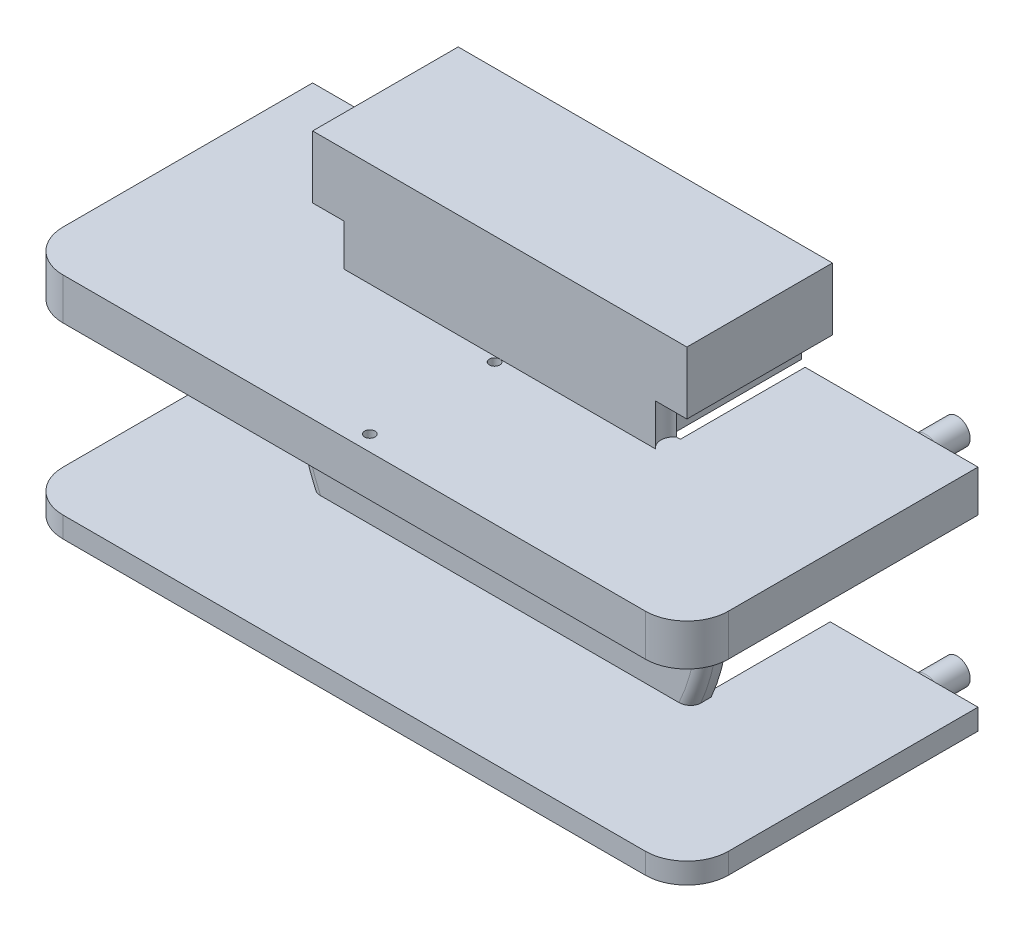
SolidWorks part; units mm, degrees
material "UNOBTANIUM"
ref_plane "Top Plane" through (0, 0, 0) normal (0, 0, 1) x (1, 0, 0)
ref_plane "Right Plane" through (0, 0, 0) normal (0, 1, 0) x (1, 0, 0)
ref_plane "Front Plane" through (0, 0, 0) normal (1, 0, 0) x (0, 0, -1)
ref_axis "x-axis" through (-17.6, 0, 0) along (1, 0, 0)
ref_axis "y-axis" through (0, -9.7375, 0) along (0, 1, 0)
ref_axis "z-axis" through (0, 0, 8.775) along (0, 0, -1)
sketch "Sketch1" plane through (0, 0, 0) normal (0, 0, 1) x (1, 0, 0)
  line L0 (-11, 6) -> (-11, 11)
  line L1 (-11, -6) -> (11, -6)
  line L2 (-11, -6) -> (-11, 6)
  line L3 (-11, 6) -> (11, 6) construction
  line L4 (11, -6) -> (11, 6)
  line L5 (-11, -6) -> (11, 6) construction
  line L6 (-11, 6) -> (11, -6) construction
  line L7 (-11, 11) -> (11, 11)
  line L8 (11, 11) -> (11, 6)
  circle A0 centre (0, 0) radius 9.25 construction
  point P0 (0, 0)
  dimension "D1" = 18.5
  dimension "D2" = 22
  dimension "D3" = 12
  dimension "D4" = 5
extrude "Boss-Extrude1" add sketch "Sketch1" along normal blind 1
sketch "Sketch2" plane through (0, 0, 0) normal (0, 0, -1) x (-1, 0, 0)
  circle A0 centre (0, 0) radius 1.51
  dimension "D1" = 3.02
extrude "Boss-Extrude2" add sketch "Sketch2" along normal blind 5.5
sketch "Sketch3" plane through (0, 0, 0) normal (0, 0, -1) x (-1, 0, 0)
  line L0 (11, -6) -> (-11, 6) construction
  circle A0 centre (0, 0) radius 3.5
  dimension "D1" = 7
extrude "Boss-Extrude3" add sketch "Sketch3" along normal blind 1
sketch "Sketch4" plane through (0, 0, 0) normal (0, 0, -1) x (-1, 0, 0)
  line L0 (11, -6) -> (-11, -6) construction
  line L1 (11, 11) -> (9, 11)
  line L2 (11, 11) -> (11, -6)
  line L3 (11, -6) -> (9, -6)
  line L4 (9, 11) -> (9, -6)
  line L5 (0, -6) -> (0, 11) construction
  line L7 (-9, 11) -> (-9, -6)
  line L8 (-11, -6) -> (-9, -6)
  line L9 (-11, 11) -> (-11, -6)
  line L10 (-11, 11) -> (-9, 11)
  line L11 (11, 11) -> (-11, 11) construction
  dimension "D1" = 2
extrude "Boss-Extrude4" add sketch "Sketch4" along normal blind 6
sketch "Sketch5" plane through (0, 0, 0) normal (0, 0, -1) x (-1, 0, 0)
  line L0 (-9, -6) -> (-9, 11) construction
  line L1 (9, 11) -> (-9, 11)
  line L2 (9, 11) -> (9, 9)
  line L3 (9, 9) -> (-9, 9)
  line L4 (-9, 11) -> (-9, 9)
  dimension "D1" = 2
extrude "Boss-Extrude5" add sketch "Sketch5" along normal up to surface (6 mm away) up to face at (-10, 2.5, -6)
sketch "Sketch6" plane through (11, 0, 0) normal (1, 0, 0) x (0, 0, -1)
  line L0 (-1, -6) -> (-1, 11) construction
  line L1 (6, -6) -> (-1, -6)
  line L2 (6, -6) -> (6, -4)
  line L3 (6, -4) -> (-1, -4)
  line L4 (-1, -6) -> (-1, -4)
  line L6 (6, 11) -> (6, -6) construction
  line L7 (-1, 6) -> (6, 6)
  line L8 (-1, 6) -> (-1, 4)
  line L9 (-1, 4) -> (6, 4)
  line L10 (6, 6) -> (6, 4)
  line L11 (2.5, 4) -> (2.5, -4) construction
  line L12 (0, 0) -> (2.5, 0) construction
  line L13 (0, -6) -> (0, 6) construction
  point P21 (2.5, 0)
  dimension "D1" = 2
extrude "Boss-Extrude6" add sketch "Sketch6" along normal blind 5
mirror "Mirror1" about plane through (0, 0, 0) normal (1, 0, 0) of "Boss-Extrude6"
sketch "Sketch7" plane through (0, 0, -6) normal (0, 0, -1) x (-1, 0, 0)
  line L0 (-9, -6) -> (-9, 9) construction
  line L1 (-9, 0) -> (-9, 9)
  line L2 (-9, 9) -> (0, 9)
  line L3 (-9, 0) -> (-9, -6)
  line L4 (-9, -6) -> (-6.7082, -6)
  line L5 (11, -6) -> (-11, -6) construction
  arc A0 (0, 9) -> (-6.7082, -6) centre (0, 0) ccw
  line M18 (-9, -6) -> (-9, 9)
  line M19 (-9, 9) -> (9, 9)
extrude "Boss-Extrude7" add sketch "Sketch7" against normal up to surface (6 mm away) contours A0 L4 M18 | A0 M19 M18 region at (8.3306, -4.5409, -6) region at (6.9897, 6.9897, -6) up to face at (3.5, 0, 0)
sketch "Sketch8" plane through (0, 0, -6) normal (0, 0, -1) x (-1, 0, 0)
  line L0 (-11, 4) -> (-9.1652, 4)
  line L1 (-11, 4) -> (-11, -4)
  line L2 (-11, -4) -> (-9.1652, -4)
  arc A1 (-9.1652, 4) -> (-9.1652, -4) centre (0, 0) ccw
  dimension "D1" = 10
extrude "Cut-Extrude1" cut sketch "Sketch8" against normal through all
sketch "Sketch9" plane through (0, 0, -6) normal (0, 0, -1) x (-1, 0, 0)
  line L0 (-16, -4) -> (-9.1652, -4) construction
  line L1 (-8.0623, 4) -> (-11, 4)
  line L2 (-8.0623, 4) -> (-8.0623, -4)
  line L3 (-8.0623, -4) -> (-11, -4)
  line L4 (-11, 4) -> (-11, -4)
  line L5 (-11, -6) -> (-11, 6) construction
  arc A0 (0, 9) -> (-6.7082, -6) centre (0, 0) ccw construction
  arc A1 (0, 9) -> (-6.7082, -6) centre (0, 0) ccw construction
extrude "Cut-Extrude2" cut sketch "Sketch9" against normal up to surface (6 mm away) up to face at (3.5, 0, 0)
mirror "Mirror2" about plane through (0, 0, 0) normal (1, 0, 0) of "Cut-Extrude2", "Cut-Extrude1", "Boss-Extrude7"
sketch "Sketch21" plane through (0, 0, -6) normal (0, 0, -1) x (-1, 0, 0)
  circle A0 centre (0, 0) radius 9.75
  circle A1 centre (0, 0) radius 9 construction
  circle A2 centre (0, 0) radius 3.5 construction
  circle A3 centre (0, 0) radius 3.5
  dimension "D1" = 0.75
extrude "Cut-Extrude11" cut sketch "Sketch21" against normal up to surface (6 mm away) up to face at (0, -0.7091, 0)
sketch "Sketch10" plane through (0, 0, 1) normal (0, 0, 1) x (1, 0, 0)
  line L0 (-16, -4) -> (-16, -6) construction
  line L1 (16, -6) -> (-16, -6)
  line L2 (16, -6) -> (16, -4)
  line L3 (16, -4) -> (-16, -4)
  line L4 (-16, -6) -> (-16, -4)
  line L5 (-16, -4) -> (-9.1652, -4) construction
  line L7 (-16, 6) -> (16, 6)
  line L8 (-16, 6) -> (-16, 4)
  line L9 (-16, 4) -> (16, 4)
  line L10 (16, 6) -> (16, 4)
extrude "Boss-Extrude8" add sketch "Sketch10" along normal blind 7
fillet "Fillet1" radius 0.5 2 edges at (10, 0, 1) (-10, 0, 1)
sketch "Sketch11" plane through (0, 0, -6) normal (0, 0, -1) x (-1, 0, 0)
  line L0 (-16, -5) -> (-13, -5) construction
  line L1 (-16, -6) -> (-16, -4) construction
  circle A0 centre (-13, -5) radius 0.625
  dimension "D1" = 1.25
  dimension "D2" = 3
extrude "Boss-Extrude9" add sketch "Sketch11" along normal blind 2
sketch "Sketch14" plane through (0, 0, -6) normal (0, 0, -1) x (-1, 0, 0)
  line L1 (11, 6) -> (7.5, 6)
  line L2 (11, 6) -> (11, 8)
  line L3 (11, 8) -> (7.5, 8)
  line L4 (7.5, 6) -> (7.5, 8)
  line L5 (-11, 6) -> (-7.5, 6)
  line L6 (-11, 6) -> (-11, 8)
  line L7 (-11, 8) -> (-7.5, 8)
  line L8 (-7.5, 6) -> (-7.5, 8)
  dimension "D1" = 15
  dimension "D2" = 2
extrude "Cut-Extrude5" cut sketch "Sketch14" against normal through all
sketch "Sketch12" plane through (0, 0, -6) normal (0, 0, -1) x (-1, 0, 0)
  line L0 (-16, -5) -> (-13, -5) construction
  line L1 (-16, -6) -> (-16, -4) construction
  line L3 (16, -5) -> (13, -5) construction
  line L4 (16, -6) -> (16, -4) construction
  circle A0 centre (13, -5) radius 0.675
  circle A1 centre (-13, -5) radius 0.625 construction
  circle A2 centre (-13, -5) radius 0.625 construction
  dimension "D1" = 1.35
  dimension "D2" = 1.25
extrude "Cut-Extrude3" cut sketch "Sketch12" against normal blind 2.5
sketch "Sketch16" plane through (0, 6, 0) normal (0, 1, 0) x (1, 0, 0)
  line L0 (-7.5, -1) -> (-7.5, 0) construction
  line L1 (-7.5, 0) -> (-7.5, -1)
  arc A1 (-7.5, 0) -> (-7.5, -1) centre (-7.875, -0.5) cw
  dimension "D1" = 0.25
  dimension "D2" = 1
extrude "Cut-Extrude6" cut sketch "Sketch16" along normal blind 2
mirror "Mirror3" about plane through (0, 0, 0) normal (0, 1, 0) of "Boss-Extrude9", "Cut-Extrude3"
mirror "Mirror4" about plane through (0, 0, 0) normal (1, 0, 0) of "Cut-Extrude6"
fillet "Fillet2" radius 0.5 2 edges at (12.375, 5, -6) (13.625, -5, -6)
fillet "Fillet3" radius 0.5 2 edges at (-13.675, 5, -6) (-13.675, -5, -6)
fillet "Fillet4" radius 2 4 edges at (16, -5, 8) (16, 5, 8) (-16, -5, 8) (-16, 5, 8)
sketch "Sketch17" plane through (0, -6, 0) normal (0, -1, 0) x (1, 0, 0)
  line L0 (-16, 6) -> (-16, -6) construction
  line L1 (-14, 8) -> (14, 8) construction
  line L2 (16, 6) -> (16, -6) construction
  line L3 (-16, 6) -> (-16, -6)
  line L4 (-14, 8) -> (14, 8)
  line L5 (16, 6) -> (16, -6)
  line L6 (14.5, 6) -> (14.5, -6)
  line L8 (-14, 6.5) -> (14, 6.5)
  line L9 (-14.5, 6) -> (-14.5, -6)
  line L10 (14.5, -6) -> (16, -6)
  line L11 (-14.5, -6) -> (-16, -6)
  arc A0 (-14, 8) -> (-16, 6) centre (-14, 6) ccw construction
  arc A1 (16, 6) -> (14, 8) centre (14, 6) ccw construction
  arc A2 (-14, 8) -> (-16, 6) centre (-14, 6) ccw
  arc A3 (16, 6) -> (14, 8) centre (14, 6) ccw
  arc A4 (14.5, 6) -> (14, 6.5) centre (14, 6) ccw
  arc A5 (-14, 6.5) -> (-14.5, 6) centre (-14, 6) ccw
  dimension "D1" = 1.5
extrude "Cut-Extrude7" cut sketch "Sketch17" against normal blind 1 and the other way through all
sketch "Sketch19" plane through (0, 6, 0) normal (0, 1, 0) x (1, 0, 0)
  line L0 (7.5, -1) -> (-7.5, -1) construction
  line L1 (0, -1.25) -> (0, -1) construction
  line L2 (7.5, -1) -> (-7.5, -1) construction
  circle A0 centre (0, -1.25) radius 0.25
  circle A1 centre (0, -7.25) radius 0.25
  point P4 (0, -1)
  dimension "D1" = 0.5
  dimension "D2" = 6
extrude "Cut-Extrude9" cut sketch "Sketch19" against normal up to surface (2 mm away) up to face at (0.0154, 4, -0.7999)
sketch "Sketch20" plane through (0, 0, -6) normal (0, 0, -1) x (-1, 0, 0)
  line L0 (-7.5, 8) -> (-11, 8) construction
  line L1 (-11, 11) -> (-9, 11)
  line L2 (-11, 11) -> (-11, 8)
  line L3 (-11, 8) -> (-9, 8)
  line L4 (-9, 11) -> (-9, 8)
  line L5 (11, 11) -> (-11, 11) construction
  line L6 (11, 8) -> (9, 8)
  line L7 (11, 8) -> (11, 11)
  line L8 (11, 11) -> (9, 11)
  line L9 (9, 8) -> (9, 11)
  dimension "D1" = 2
extrude "Cut-Extrude10" cut sketch "Sketch20" against normal through all
equation "\"D1@Sketch12\"=\"D2@Sketch12\"+.1"
